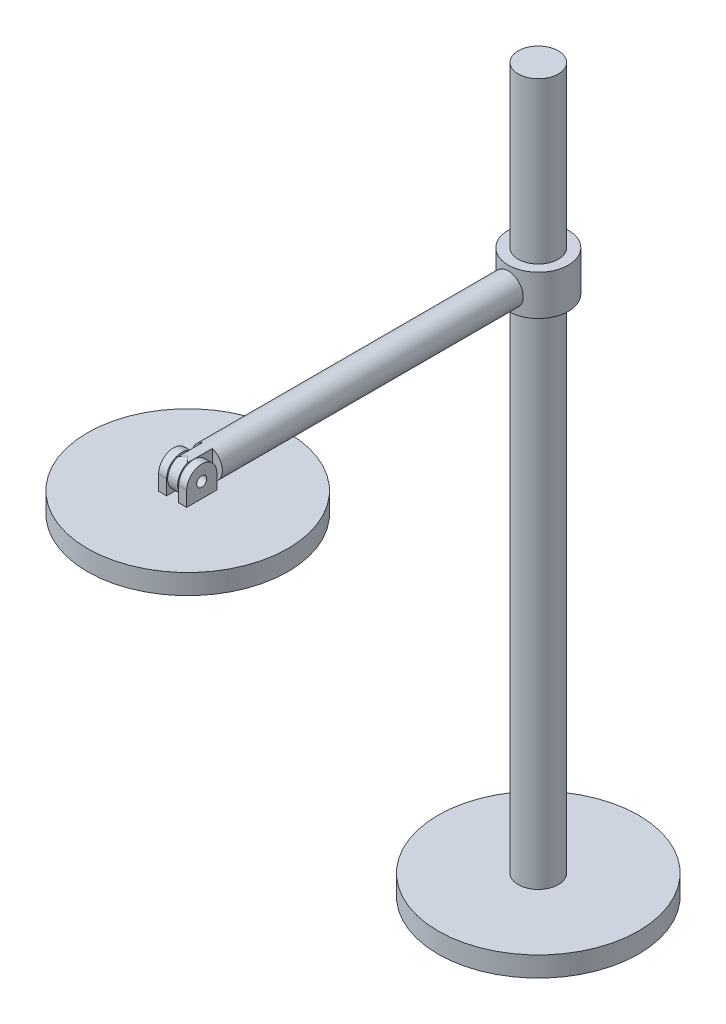
SolidWorks part; units mm, degrees
ref_plane "Front Plane" through (0, 0, 0) normal (0, 0, 1) x (1, 0, 0)
ref_plane "Top Plane" through (0, 0, 0) normal (0, 1, 0) x (1, 0, 0)
ref_plane "Right Plane" through (0, 0, 0) normal (1, 0, 0) x (0, 0, -1)
sketch "Sketch1" plane through (0, 0, 0) normal (0, 1, 0) x (1, 0, 0)
  circle A0 centre (0, 0) radius 50
  dimension "D1" = 100
extrude "Boss-Extrude1" add sketch "Sketch1" along normal blind 10 contours A0 region at (0, 0, 0)
sketch "Sketch2" plane through (0, 10, 0) normal (0, 1, 0) x (1, 0, 0)
  circle A0 centre (0, 0) radius 10
  dimension "D1" = 20
extrude "Boss-Extrude2" add sketch "Sketch2" along normal blind 350 contours A0 region at (0, 10, 0)
ref_plane "Plane1" through (0, 260, 0) normal (0, 1, 0) x (1, 0, 0)
sketch "Sketch3" plane through (0, 260, 0) normal (0, 1, 0) x (1, 0, 0)
  circle A0 centre (0, 0) radius 15
  circle A1 centre (0, 0) radius 10
  circle A2 centre (0, 0) radius 10
  dimension "D2" = 30
  dimension "D1" = 0
extrude "Boss-Extrude3" add sketch "Sketch3" along normal blind 20 contours A0 A2 region at (-14.5757, 260, 0)
ref_plane "Plane2" through (0, 0, 15) normal (0, 0, 1) x (1, 0, 0)
sketch "Sketch4" plane through (0, 0, 15) normal (0, 0, 1) x (1, 0, 0)
  line L0 (15, 260) -> (15, 280) construction
  line L1 (15, 260) -> (15, 280)
  circle A0 centre (0, 270) radius 7.5
  point P2 (0, 0)
  point P5 (15, 270)
  dimension "D1" = 15
extrude "Boss-Extrude4" add sketch "Sketch4" along normal blind 150 separate body contours A0 region at (0, 270, 15)
sketch "Sketch5" plane through (0, 0, 0) normal (1, 0, 0) x (0, 0, -1)
  line L1 (-165, 277.5) -> (-174.7807, 277.5)
  line L2 (-165, 277.5) -> (-165, 262.5)
  line L3 (-165, 262.5) -> (-174.7807, 262.5)
  line L4 (-174.7807, 277.5) -> (-174.7807, 262.5)
  line L5 (-182.2807, 270) -> (-167.2807, 270)
  line L6 (-182.2807, 270) -> (-182.2807, 262.5)
  line L7 (-182.2807, 262.5) -> (-167.2807, 262.5)
  line L8 (-167.2807, 270) -> (-167.2807, 262.5)
  line L9 (-174.7807, 262.5) -> (-124.7807, 262.5)
  line L10 (-174.7807, 262.5) -> (-174.7807, 252.5)
  line L11 (-174.7807, 252.5) -> (-124.7807, 252.5)
  line L12 (-124.7807, 262.5) -> (-124.7807, 252.5)
  arc A0 (-174.7807, 277.5) -> (-174.7807, 262.5) centre (-174.7807, 270) ccw
  circle A1 centre (-174.7807, 270) radius 2.5
  arc A2 (-167.2807, 270) -> (-174.7807, 262.5) centre (-174.7807, 270) ccw
  dimension "D1" = 5
  dimension "D2" = 50
  dimension "D3" = 10
extrude "Boss-Extrude5" add sketch "Sketch5" along normal mid plane 5 contours A2 L8 L3 L2 L1 | L5 A2 L4 A1 | A1 L4 L3 L8 L5 | A1 L5 A0 L4 | A1 L4 A0 L5 region at (0, 271.5192, 166.8747) region at (0, 273.4484, 171.3323) region at (0, 273.4484, 178.2291) region at (0, 266.5516, 178.2291) region at (0, 265.9929, 170.7736)
sketch "Sketch6" plane through (0, 0, 165) normal (0, 0, 1) x (1, 0, 0)
  line L1 (2.5, 277.0711) -> (2.5, 262.9289)
  circle A0 centre (0, 270) radius 7.5
  arc A1 (2.5, 262.9289) -> (2.5, 277.0711) centre (0, 270) ccw
  arc A2 (2.5, 262.9289) -> (2.5, 277.0711) centre (0, 270) ccw
  circle A3 centre (0, 270) radius 48.1584
  arc M3 (2.5, 262.9289) -> (2.5, 277.0711) centre (0, 270) ccw
  dimension "D1" = 0
extrude "Cut-Extrude1" cut sketch "Sketch6" along normal blind 15 contours A3 A0 M3 region at (-46.7963, 270, 165)
extrude "Boss-Extrude6" add sketch "Sketch5<3>" along normal blind 4 from offset 3 separate body contours L5 A2 L4 A1 | A1 L4 A0 L5 | A1 L5 A0 L4 | A0 L6 L7 | A1 L4 L3 L8 L5 region at (0, 273.4484, 171.3323) region at (0, 273.4484, 178.2291) region at (0, 264.1753, 180.6054) region at (0, 266.5516, 178.2291) region at (0, 265.9929, 170.7736)
sketch "Sketch5<3>" plane through (0, 0, 0) normal (1, 0, 0) x (0, 0, -1) same geometry as "Sketch5"
extrude "Boss-Extrude7" add sketch "Sketch5<4>" against normal blind 4 from offset 3 separate body contours L5 A2 L4 A1 | A1 L4 A0 L5 | A1 L5 A0 L4 | A1 L4 L3 L8 L5 | A0 L6 L7 region at (0, 273.4484, 171.3323) region at (0, 273.4484, 178.2291) region at (0, 264.1753, 180.6054) region at (0, 266.5516, 178.2291) region at (0, 265.9929, 170.7736) offset against normal yes
sketch "Sketch5<4>" plane through (0, 0, 0) normal (1, 0, 0) x (0, 0, -1) same geometry as "Sketch5"
revolve "Revolve1" add sketch "Sketch5<5>" angle 360 about L10 region at (0, 257.5, 149.7807)
sketch "Sketch5<5>" plane through (0, 0, 0) normal (1, 0, 0) x (0, 0, -1) same geometry as "Sketch5"
sketch "Sketch7" plane through (0, 252.5, 0) normal (0, -1, 0) x (1, 0, 0)
  circle A2 centre (0, 174.7807) radius 40
  circle A3 centre (0, 174.7807) radius 40
  dimension "D1" = 10
extrude "Cut-Extrude2" cut sketch "Sketch7" against normal blind 2
